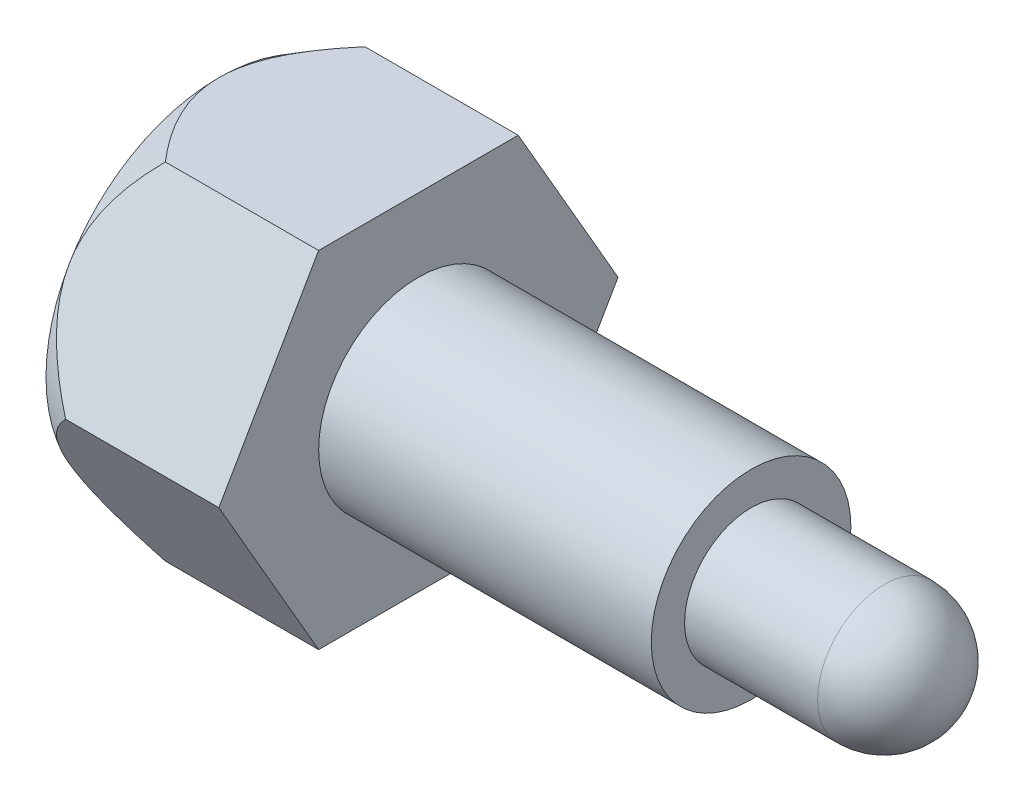
SolidWorks part; units mm, degrees
ref_plane "Front Plane" through (0, 0, 0) normal (0, 0, 1) x (1, 0, 0)
ref_plane "Top Plane" through (0, 0, 0) normal (0, 1, 0) x (1, 0, 0)
ref_plane "Right Plane" through (0, 0, 0) normal (1, 0, 0) x (0, 0, -1)
sketch "Sketch1" plane through (0, 0, 0) normal (0, 1, 0) x (1, 0, 0)
  line L0 (-1048.463, 0) -> (1048.463, 0) construction
  line L1 (0, 0) -> (0, 60)
  line L2 (0, 60) -> (60, 60)
  line L3 (-1016.4202, -0.1076) -> (1080.5059, -0.1076) construction
  line L4 (0, 0) -> (200, 0)
  line L5 (60, 60) -> (60, 30)
  line L6 (60, 30) -> (160, 30)
  line L7 (160, 30) -> (160, 20)
  line L8 (160, 20) -> (200, 20)
  line L9 (200, 20) -> (200, 0)
  point P3 (0, 0)
  dimension "D1" = 60
  dimension "D2" = 200
  dimension "D3" = 100
  dimension "D4" = 60
  dimension "D5" = 20
  dimension "D6" = 30
revolve "Revolve2" add sketch "Sketch1" angle 360 about L4 other way angle 360
dome "Dome1" faces to dome 1 distance 20 reverse direction no elliptical dome no face at (200, 0, 20) parameters "D1"=20
sketch "Sketch3" plane through (0, 0, 0) normal (-1, 0, 0) x (0, 0, 1)
  line L1 (60, 0) -> (30, 51.9615)
  line L2 (30, 51.9615) -> (-30, 51.9615)
  line L3 (-30, 51.9615) -> (-60, 0)
  line L4 (-60, 0) -> (-30, -51.9615)
  line L5 (-30, -51.9615) -> (30, -51.9615)
  line L6 (30, -51.9615) -> (60, 0)
  circle A0 centre (0, 0) radius 51.9615 construction
  dimension "D2" = 103.923
  dimension "D1" = 60
chamfer "Chamfer1" [suppressed] distance 5 angle 30
extrude "Cut-Extrude4" cut sketch "Sketch3" against normal through all flip side to cut
sketch "Sketch5" plane through (0, 0, 0) normal (-1, 0, 0) x (0, 0, 1)
  circle A0 centre (0, 0) radius 51.9615
extrude "Cut-Extrude5" cut sketch "Sketch5" against normal through all draft 30 flip side to cut contours A0
